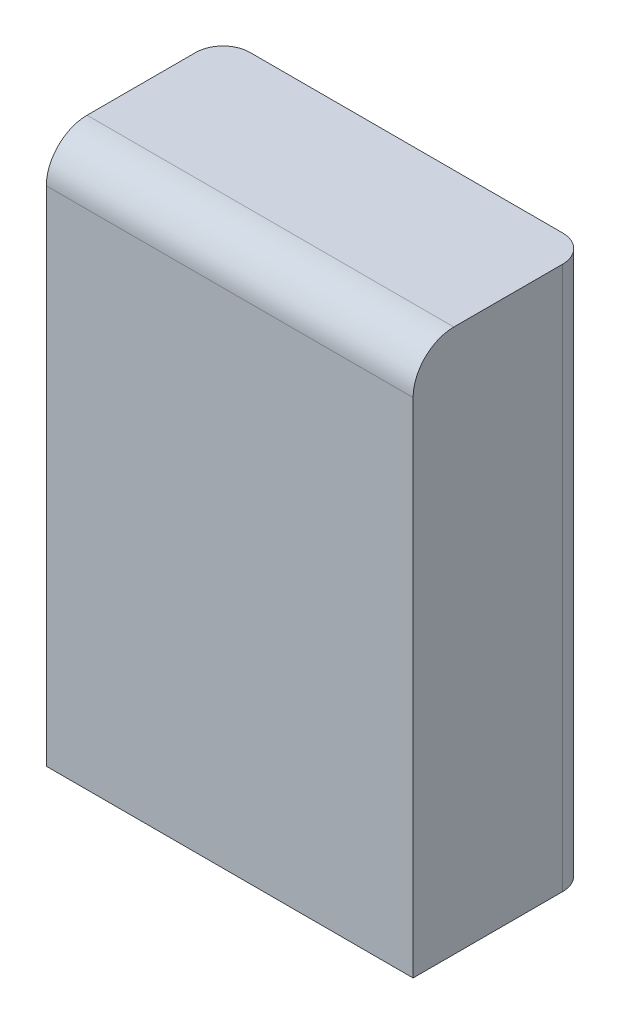
SolidWorks part; units mm, degrees
material "K110"
ref_plane "Front Plane" through (0, 0, 0) normal (0, 0, 1) x (1, 0, 0)
ref_plane "Top Plane" through (0, 0, 0) normal (0, 1, 0) x (1, 0, 0)
ref_plane "Right Plane" through (0, 0, 0) normal (1, 0, 0) x (0, 0, -1)
sketch "Sketch1" plane through (0, 0, 0) normal (0, 1, 0) x (1, 0, 0)
  line L1 (-13.5, -6.5) -> (13.5, -6.5)
  line L2 (-13.5, -6.5) -> (-13.5, 6.5)
  line L3 (-13.5, 6.5) -> (13.5, 6.5)
  line L4 (13.5, -6.5) -> (13.5, 6.5)
  line L5 (-13.5, -6.5) -> (13.5, 6.5) construction
  line L6 (-13.5, 6.5) -> (13.5, -6.5) construction
  point P0 (0, 0)
  dimension "D1" = 13
  dimension "D2" = 27
extrude "Boss-Extrude1" add sketch "Sketch1" against normal blind 40
fillet "Fillet1" radius 2 2 edges at (-13.5, -20, -6.5) (13.5, -20, -6.5)
fillet "Fillet2" radius 3 1 edges at (0, 0, 6.5) tangent propagation no
hole_wizard "M6 Tapped Hole1" positions "Sketch4" profile "Sketch3" tap size "M6" standard "ISO"
sketch "Sketch4" plane through (0, -40, 0) normal (0, -1, 0) x (-1, 0, 0)
  line L0 (-13.5, -6.5) -> (-13.5, 4.5) construction
  line L1 (13.5, 4.5) -> (13.5, -6.5) construction
  point P0 (-6, 0)
  point P2 (6, 0)
  dimension "D1" = 7.5
  dimension "D2" = 7.5
sketch "Sketch3" plane through (6, -40, 0) normal (1, 0, 0) x (0, 0, -1)
  line L0 (0, 0) -> (0, 18.5022)
  line L1 (0, 18.5022) -> (2.5, 17)
  line L2 (2.5, 17) -> (2.5, 0.525)
  line L3 (2.5, 0.525) -> (3.025, 0)
  line L5 (3.025, 0) -> (0, 0)
  line L6 (-2.5, 0.525) -> (-3.025, 0) construction
  line L10 (0, 18.5022) -> (-2.5, 17) construction
  line L11 (0, -6.35) -> (0, 107.95) construction
  dimension "Tap Drill Dia." = 5
  dimension "Tap Drill Depth" = 17
  dimension "Near C'Sink Dia." = 6.05
  dimension "Near C'Sink Angle" = 90
  dimension "Drill Angle" = 118
cosmetic thread "Hole Thread1"
cosmetic thread "Hole Thread2"
